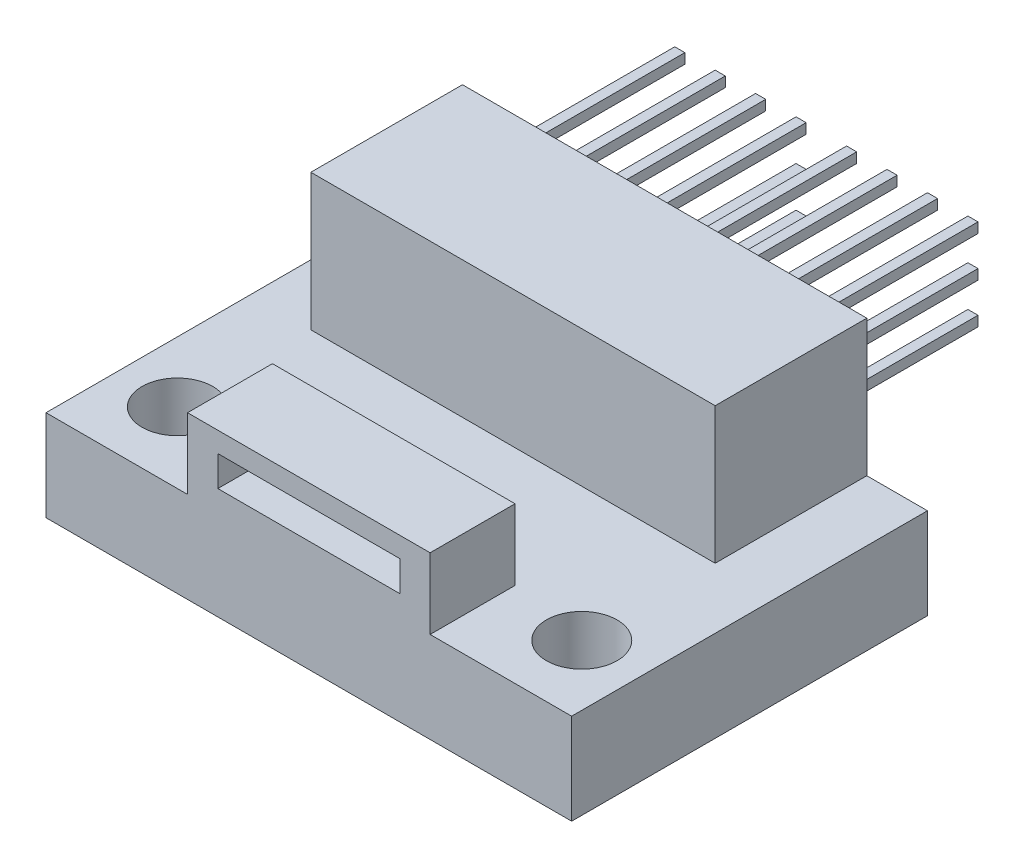
SolidWorks part; units mm, degrees
ref_plane "Front Plane" through (0, 0, 0) normal (0, 0, 1) x (1, 0, 0)
ref_plane "Top Plane" through (0, 0, 0) normal (0, 1, 0) x (1, 0, 0)
ref_plane "Right Plane" through (0, 0, 0) normal (1, 0, 0) x (0, 0, -1)
sketch "Sketch1" plane through (0, 0, 0) normal (0, 1, 0) x (1, 0, 0)
  line L0 (0, 8.8) -> (0, -8.8) construction
  line L1 (-13, 8.8) -> (13, 8.8)
  line L2 (-13, 8.8) -> (-13, -8.8)
  line L3 (-13, -8.8) -> (13, -8.8)
  line L4 (13, 8.8) -> (13, -8.8)
  line L5 (-13, 8.8) -> (13, -8.8) construction
  line L6 (-13, -8.8) -> (13, 8.8) construction
  line L7 (-13, 0) -> (13, 0) construction
  circle A0 centre (10, -5.3) radius 1.75
  circle A1 centre (-10, -5.3) radius 1.75
  point P0 (0, 0)
  dimension "D3" = 3.5
  dimension "D1" = 17.6
  dimension "D2" = 26
  dimension "D4" = 10
  dimension "D5" = 3.5
extrude "Boss-Extrude1" add sketch "Sketch1" along normal blind 4.5
sketch "Sketch2" plane through (0, 4.5, 0) normal (0, 1, 0) x (1, 0, 0)
  line L0 (0, 8.8) -> (0, -8.8) construction
  line L1 (13, 8.8) -> (-13, 8.8) construction
  line L2 (-13, -8.8) -> (13, -8.8) construction
  line L4 (-6, -4.6) -> (6, -4.6)
  line L5 (-6, -4.6) -> (-6, -8.8)
  line L6 (-6, -8.8) -> (6, -8.8)
  line L7 (6, -4.6) -> (6, -8.8)
  line L8 (-6, -4.6) -> (6, -8.8) construction
  line L9 (-6, -8.8) -> (6, -4.6) construction
  point P6 (0, -6.7)
  dimension "D1" = 4.2
  dimension "D2" = 12
extrude "Boss-Extrude2" add sketch "Sketch2" along normal blind 3.5
sketch "Sketch3" plane through (0, 0, 8.8) normal (0, 0, 1) x (1, 0, 0)
  line L0 (-6, 6.25) -> (6, 6.25) construction
  line L1 (-6, 8) -> (-6, 4.5) construction
  line L2 (6, 8) -> (6, 4.5) construction
  line L4 (-4.5, 7) -> (4.5, 7)
  line L5 (-4.5, 7) -> (-4.5, 5.5)
  line L6 (-4.5, 5.5) -> (4.5, 5.5)
  line L7 (4.5, 7) -> (4.5, 5.5)
  line L8 (-4.5, 7) -> (4.5, 5.5) construction
  line L9 (-4.5, 5.5) -> (4.5, 7) construction
  point P6 (0, 6.25)
  dimension "D1" = 9
  dimension "D2" = 1.5
extrude "Cut-Extrude1" cut sketch "Sketch3" against normal blind 1.5
sketch "Sketch4" plane through (0, 4.5, 0) normal (0, 1, 0) x (1, 0, 0)
  line L0 (0, 8.8) -> (0, -8.8) construction
  line L1 (13, 8.8) -> (-13, 8.8) construction
  line L2 (-6, -8.8) -> (6, -8.8) construction
  line L4 (-10, 1.3) -> (10, 1.3)
  line L5 (-10, 1.3) -> (-10, 8.8)
  line L6 (-10, 8.8) -> (10, 8.8)
  line L7 (10, 1.3) -> (10, 8.8)
  line L8 (-10, 1.3) -> (10, 8.8) construction
  line L9 (-10, 8.8) -> (10, 1.3) construction
  point P6 (0, 5.05)
  dimension "D1" = 7.5
  dimension "D2" = 20
extrude "Boss-Extrude3" add sketch "Sketch4" along normal blind 6.75
sketch "Sketch5" plane through (0, 0, -8.8) normal (0, 0, -1) x (-1, 0, 0)
  line L0 (0, 0) -> (0, 11.25) construction
  line L1 (-10, 11.25) -> (10, 11.25) construction
  line L2 (-10, 7.875) -> (10, 7.875) construction
  line L3 (-10, 11.25) -> (-10, 4.5) construction
  line L4 (10, 11.25) -> (10, 4.5) construction
  line L5 (3, 8.125) -> (3.5, 8.125)
  line L6 (1, 8.125) -> (1.5, 8.125)
  line L7 (1, 8.125) -> (1, 7.625)
  line L8 (1, 7.625) -> (1.5, 7.625)
  line L9 (1.5, 8.125) -> (1.5, 7.625)
  line L10 (1, 8.125) -> (1.5, 7.625) construction
  line L11 (1, 7.625) -> (1.5, 8.125) construction
  line L12 (3, 8.125) -> (3, 7.625)
  line L13 (3, 7.625) -> (3.5, 7.625)
  line L14 (3.5, 8.125) -> (3.5, 7.625)
  line L15 (3, 8.125) -> (3.5, 7.625) construction
  line L16 (3, 7.625) -> (3.5, 8.125) construction
  line L17 (5, 8.125) -> (5.5, 8.125)
  line L18 (5, 8.125) -> (5, 7.625)
  line L19 (5, 7.625) -> (5.5, 7.625)
  line L20 (5.5, 8.125) -> (5.5, 7.625)
  line L21 (5, 8.125) -> (5.5, 7.625) construction
  line L22 (5, 7.625) -> (5.5, 8.125) construction
  line L23 (7, 8.125) -> (7.5, 8.125)
  line L24 (7, 8.125) -> (7, 7.625)
  line L25 (7, 7.625) -> (7.5, 7.625)
  line L26 (7.5, 8.125) -> (7.5, 7.625)
  line L27 (7, 8.125) -> (7.5, 7.625) construction
  line L28 (7, 7.625) -> (7.5, 8.125) construction
  line L29 (-7, 7.625) -> (-7.5, 8.125) construction
  line L30 (-7, 8.125) -> (-7.5, 7.625) construction
  line L31 (-5, 7.625) -> (-5.5, 8.125) construction
  line L32 (-5, 8.125) -> (-5.5, 7.625) construction
  line L33 (-3, 7.625) -> (-3.5, 8.125) construction
  line L34 (-3, 8.125) -> (-3.5, 7.625) construction
  line L35 (-1, 7.625) -> (-1.5, 8.125) construction
  line L36 (-1, 8.125) -> (-1.5, 7.625) construction
  line L37 (-7.5, 8.125) -> (-7.5, 7.625)
  line L38 (-7, 7.625) -> (-7.5, 7.625)
  line L39 (-7, 8.125) -> (-7, 7.625)
  line L40 (-7, 8.125) -> (-7.5, 8.125)
  line L41 (-5.5, 8.125) -> (-5.5, 7.625)
  line L42 (-5, 7.625) -> (-5.5, 7.625)
  line L43 (-5, 8.125) -> (-5, 7.625)
  line L44 (-5, 8.125) -> (-5.5, 8.125)
  line L45 (-3.5, 8.125) -> (-3.5, 7.625)
  line L46 (-3, 7.625) -> (-3.5, 7.625)
  line L47 (-3, 8.125) -> (-3, 7.625)
  line L48 (-1.5, 8.125) -> (-1.5, 7.625)
  line L49 (-1, 7.625) -> (-1.5, 7.625)
  line L50 (-1, 8.125) -> (-1, 7.625)
  line L51 (-1, 8.125) -> (-1.5, 8.125)
  line L52 (-3, 8.125) -> (-3.5, 8.125)
  line L53 (-10, 8.875) -> (10, 8.875) construction
  line L54 (-10, 6.875) -> (10, 6.875) construction
  line L55 (-1, 9.625) -> (-1.5, 10.125) construction
  line L56 (-1, 10.125) -> (-1.5, 9.625) construction
  line L57 (-3, 9.625) -> (-3.5, 10.125) construction
  line L58 (-3, 10.125) -> (-3.5, 9.625) construction
  line L59 (-5, 9.625) -> (-5.5, 10.125) construction
  line L60 (-5, 10.125) -> (-5.5, 9.625) construction
  line L61 (-7, 9.625) -> (-7.5, 10.125) construction
  line L62 (-7, 10.125) -> (-7.5, 9.625) construction
  line L63 (7, 10.125) -> (7.5, 9.625) construction
  line L64 (7, 9.625) -> (7.5, 10.125) construction
  line L65 (5, 10.125) -> (5.5, 9.625) construction
  line L66 (5, 9.625) -> (5.5, 10.125) construction
  line L67 (3, 10.125) -> (3.5, 9.625) construction
  line L68 (3, 9.625) -> (3.5, 10.125) construction
  line L69 (1, 10.125) -> (1.5, 9.625) construction
  line L70 (1, 9.625) -> (1.5, 10.125) construction
  line L71 (-3, 9.625) -> (-3.5, 9.625)
  line L72 (-1, 9.625) -> (-1.5, 9.625)
  line L73 (-1, 9.625) -> (-1, 10.125)
  line L74 (-1, 10.125) -> (-1.5, 10.125)
  line L75 (-1.5, 9.625) -> (-1.5, 10.125)
  line L76 (-3, 9.625) -> (-3, 10.125)
  line L77 (-3, 10.125) -> (-3.5, 10.125)
  line L78 (-3.5, 9.625) -> (-3.5, 10.125)
  line L79 (-5, 9.625) -> (-5.5, 9.625)
  line L80 (-5, 9.625) -> (-5, 10.125)
  line L81 (-5, 10.125) -> (-5.5, 10.125)
  line L82 (-5.5, 9.625) -> (-5.5, 10.125)
  line L83 (-7, 9.625) -> (-7.5, 9.625)
  line L84 (-7, 9.625) -> (-7, 10.125)
  line L85 (-7, 10.125) -> (-7.5, 10.125)
  line L86 (-7.5, 9.625) -> (-7.5, 10.125)
  line L87 (7.5, 9.625) -> (7.5, 10.125)
  line L88 (7, 10.125) -> (7.5, 10.125)
  line L89 (7, 9.625) -> (7, 10.125)
  line L90 (7, 9.625) -> (7.5, 9.625)
  line L91 (5.5, 9.625) -> (5.5, 10.125)
  line L92 (5, 10.125) -> (5.5, 10.125)
  line L93 (5, 9.625) -> (5, 10.125)
  line L94 (5, 9.625) -> (5.5, 9.625)
  line L95 (3.5, 9.625) -> (3.5, 10.125)
  line L96 (3, 10.125) -> (3.5, 10.125)
  line L97 (3, 9.625) -> (3, 10.125)
  line L98 (1.5, 9.625) -> (1.5, 10.125)
  line L99 (1, 10.125) -> (1.5, 10.125)
  line L100 (1, 9.625) -> (1, 10.125)
  line L101 (1, 9.625) -> (1.5, 9.625)
  line L102 (3, 9.625) -> (3.5, 9.625)
  line L103 (-1, 5.625) -> (-1.5, 6.125) construction
  line L104 (-1, 6.125) -> (-1.5, 5.625) construction
  line L105 (-3, 5.625) -> (-3.5, 6.125) construction
  line L106 (-3, 6.125) -> (-3.5, 5.625) construction
  line L107 (-5, 5.625) -> (-5.5, 6.125) construction
  line L108 (-5, 6.125) -> (-5.5, 5.625) construction
  line L109 (-7, 5.625) -> (-7.5, 6.125) construction
  line L110 (-7, 6.125) -> (-7.5, 5.625) construction
  line L111 (7, 6.125) -> (7.5, 5.625) construction
  line L112 (7, 5.625) -> (7.5, 6.125) construction
  line L113 (5, 6.125) -> (5.5, 5.625) construction
  line L114 (5, 5.625) -> (5.5, 6.125) construction
  line L115 (3, 6.125) -> (3.5, 5.625) construction
  line L116 (3, 5.625) -> (3.5, 6.125) construction
  line L117 (1, 6.125) -> (1.5, 5.625) construction
  line L118 (1, 5.625) -> (1.5, 6.125) construction
  line L119 (-3, 5.625) -> (-3.5, 5.625)
  line L120 (-1, 5.625) -> (-1.5, 5.625)
  line L121 (-1, 5.625) -> (-1, 6.125)
  line L122 (-1, 6.125) -> (-1.5, 6.125)
  line L123 (-1.5, 5.625) -> (-1.5, 6.125)
  line L124 (-3, 5.625) -> (-3, 6.125)
  line L125 (-3, 6.125) -> (-3.5, 6.125)
  line L126 (-3.5, 5.625) -> (-3.5, 6.125)
  line L127 (-5, 5.625) -> (-5.5, 5.625)
  line L128 (-5, 5.625) -> (-5, 6.125)
  line L129 (-5, 6.125) -> (-5.5, 6.125)
  line L130 (-5.5, 5.625) -> (-5.5, 6.125)
  line L131 (-7, 5.625) -> (-7.5, 5.625)
  line L132 (-7, 5.625) -> (-7, 6.125)
  line L133 (-7, 6.125) -> (-7.5, 6.125)
  line L134 (-7.5, 5.625) -> (-7.5, 6.125)
  line L135 (7.5, 5.625) -> (7.5, 6.125)
  line L136 (7, 6.125) -> (7.5, 6.125)
  line L137 (7, 5.625) -> (7, 6.125)
  line L138 (7, 5.625) -> (7.5, 5.625)
  line L139 (5.5, 5.625) -> (5.5, 6.125)
  line L140 (5, 6.125) -> (5.5, 6.125)
  line L141 (5, 5.625) -> (5, 6.125)
  line L142 (5, 5.625) -> (5.5, 5.625)
  line L143 (3.5, 5.625) -> (3.5, 6.125)
  line L144 (3, 6.125) -> (3.5, 6.125)
  line L145 (3, 5.625) -> (3, 6.125)
  line L146 (1.5, 5.625) -> (1.5, 6.125)
  line L147 (1, 6.125) -> (1.5, 6.125)
  line L148 (1, 5.625) -> (1, 6.125)
  line L149 (1, 5.625) -> (1.5, 5.625)
  line L150 (3, 5.625) -> (3.5, 5.625)
  point P11 (1.25, 7.875)
  point P18 (3.25, 7.875)
  point P23 (5.25, 7.875)
  point P28 (7.25, 7.875)
  point P47 (-7.25, 7.875)
  point P48 (-5.25, 7.875)
  point P49 (-3.25, 7.875)
  point P50 (-1.25, 7.875)
  point P87 (-1.25, 9.875)
  point P88 (-3.25, 9.875)
  point P89 (-5.25, 9.875)
  point P90 (-7.25, 9.875)
  point P91 (7.25, 9.875)
  point P92 (5.25, 9.875)
  point P93 (3.25, 9.875)
  point P94 (1.25, 9.875)
  point P127 (-1.25, 5.875)
  point P128 (-3.25, 5.875)
  point P129 (-5.25, 5.875)
  point P130 (-7.25, 5.875)
  point P131 (7.25, 5.875)
  point P132 (5.25, 5.875)
  point P133 (3.25, 5.875)
  point P134 (1.25, 5.875)
  dimension "D1" = 0.5
  dimension "D2" = 0.5
  dimension "D3" = 1
  dimension "D5" = 1
  dimension "D6" = 1
  dimension "D4" = 4
extrude "Boss-Extrude4" add sketch "Sketch5" along normal blind 8
